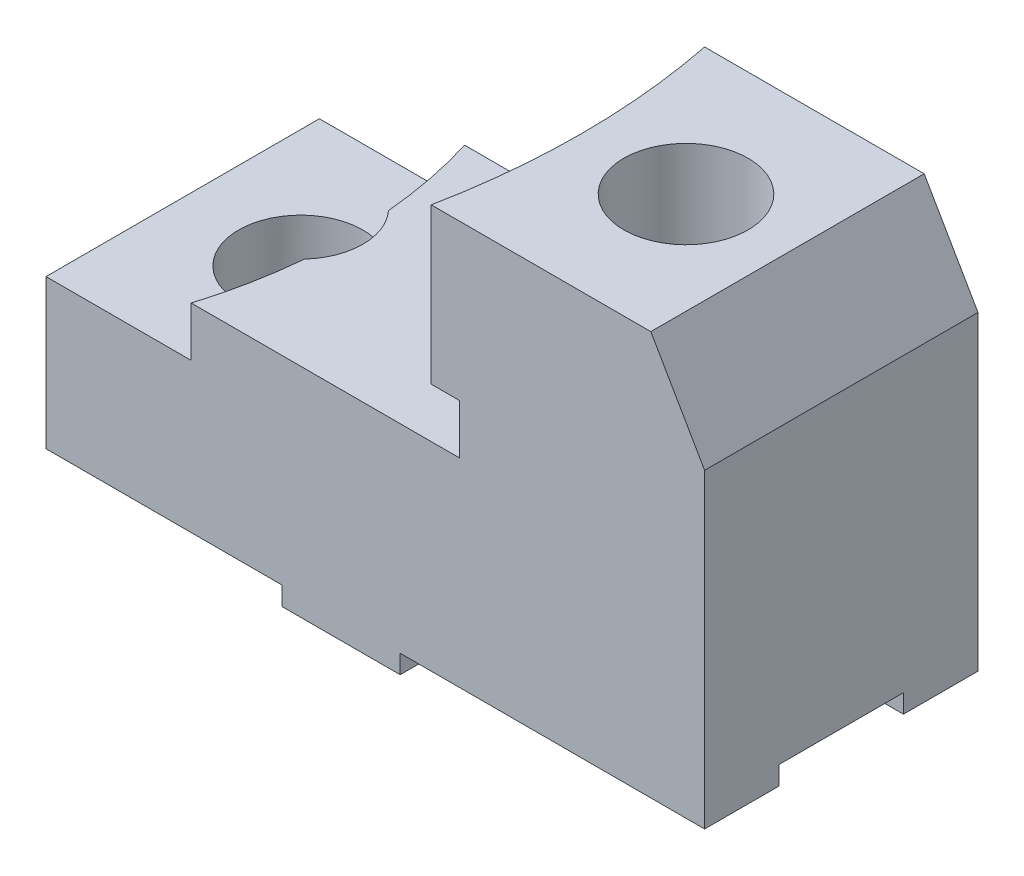
SolidWorks part; units mm, degrees
ref_plane "Front Plane" through (0, 0, 0) normal (0, 0, 1) x (1, 0, 0)
ref_plane "Top Plane" through (0, 0, 0) normal (0, 1, 0) x (1, 0, 0)
ref_plane "Right Plane" through (0, 0, 0) normal (1, 0, 0) x (0, 0, -1)
sketch "Sketch1" plane through (0, 0, 0) normal (0, 0, 1) x (1, 0, 0)
  line L0 (0, 54.6637) -> (0, -50.0258) construction
  line L1 (-88.8798, 0) -> (95.795, 0) construction
  line L10 (-47.5, -12) -> (-47.5, 12)
  line L11 (-47.5, 12) -> (58.5, 12)
  line L12 (58.5, 12) -> (58.5, -12)
  line L13 (58.5, -12) -> (9.5, -12)
  line L14 (9.5, -12) -> (9.5, -15)
  line L15 (9.5, -15) -> (-9.5, -15)
  line L16 (-9.5, -15) -> (-9.5, -12)
  line L17 (-9.5, -12) -> (-47.5, -12)
  dimension "D1" = 27
  dimension "D2" = 3
  dimension "D3" = 106
  dimension "D4" = 19
  dimension "D5" = 38
extrude "base" add sketch "Sketch1" against normal blind 44
sketch "Sketch2" plane through (0, 12, 0) normal (0, 1, 0) x (1, 0, 0)
  line L0 (-187.7294, 22) -> (123.8931, 22) construction
  line L1 (0, 66.7065) -> (0, -35.5401) construction
  line L2 (58.5, 44) -> (-47.5, 44) construction
  line L4 (-24.1272, 44) -> (14.5, 44)
  line L5 (-24.1272, 0) -> (14.5, 0)
  line L6 (58.5, 0) -> (-47.5, 0) construction
  line L7 (14.5, 44) -> (19.0851, 44)
  line L8 (14.5, 0) -> (19.0851, 0)
  line L10 (-47.5, 44) -> (-47.5, 0) construction
  arc A0 (-24.1272, 44) -> (-24.1272, 0) centre (-95.8279, 22) cw
  arc A1 (14.5, 44) -> (14.5, 0) centre (-95.8279, 22) cw
  arc A2 (14.5, 44) -> (14.5, 0) centre (-95.8279, 22) cw
  arc A3 (14.5, 44) -> (14.5, 0) centre (-95.8279, 22) cw
  arc A4 (19.0851, 0) -> (19.0851, 44) centre (-95.8279, 22) ccw
  circle A5 centre (-28.5, 22) radius 10
  circle A6 centre (-28.5, 22) radius 6.5
  line M7 (-47.5, 0) -> (58.5, 0)
  line M8 (58.5, 0) -> (58.5, 44)
  line M9 (58.5, 44) -> (-47.5, 44)
  dimension "D1" = 75
  dimension "D2" = 112.5
  dimension "D3" = 44
  dimension "D4" = 117
  dimension "D5" = 20
  dimension "D6" = 13
  dimension "D7" = 19
extrude "middle level" add sketch "Sketch2<4>" along normal blind 8 contours A5 A0 A1 M7 M9 | A4 A1 M7 M9 region at (-2.7669, 12, -22) region at (18.2114, 12, -22)
sketch "Sketch2<4>" plane through (0, 12, 0) normal (0, 1, 0) x (1, 0, 0) same geometry as "Sketch2"
extrude "up level" add sketch "Sketch2" along normal blind 41 contours A4 M7 M8 M9 region at (39.4844, 12, -22)
extrude "angle level" add sketch "Sketch2<6>" against normal blind 25 from surface contours A4 A1 M7 M9 region at (18.2114, 12, -22) starting at face at (39.3143, 53, -22)
sketch "Sketch2<6>" plane through (0, 12, 0) normal (0, 1, 0) x (1, 0, 0) same geometry as "Sketch2"
extrude "big cyl" cut sketch "Sketch2<7>" against normal blind 22 from surface contours A0 A5 | A0 A6 A5 region at (-19.9473, 12, -22) region at (-21.0948, 12, -22) starting at face at (-7.8066, 20, -22)
sketch "Sketch2<7>" plane through (0, 12, 0) normal (0, 1, 0) x (1, 0, 0) same geometry as "Sketch2"
extrude "small cyl" cut sketch "Sketch2<8>" against normal through all contours A6 region at (-28.5, 12, -22)
sketch "Sketch2<8>" plane through (0, 12, 0) normal (0, 1, 0) x (1, 0, 0) same geometry as "Sketch2"
sketch "Sketch5" plane through (0, 53, 0) normal (0, 1, 0) x (1, 0, 0)
  line L0 (-79.8364, 22) -> (59.3901, 22) construction
  line L1 (0, 60.2658) -> (0, -20.9817) construction
  line L2 (14.5, 0) -> (58.5, 0) construction
  line L3 (58.5, 44) -> (14.5, 44) construction
  circle A0 centre (33.5, 22) radius 10
  circle A1 centre (33.5, 22) radius 6.5
  dimension "D1" = 20
  dimension "D2" = 13
  dimension "D3" = 62
extrude "big cyl 2" cut sketch "Sketch5" against normal blind 22
extrude "small cyl 2" cut sketch "Sketch5<2>" against normal through all contours A1 region at (33.5, 53, -22)
sketch "Sketch5<2>" plane through (0, 53, 0) normal (0, 1, 0) x (1, 0, 0) same geometry as "Sketch5"
sketch "Sketch6" plane through (0, 0, 0) normal (0, 0, 1) x (1, 0, 0)
  line L0 (49.8397, 53) -> (58.5, 38)
  line L1 (14.5, 53) -> (58.5, 53) construction
  line L2 (58.5, -12) -> (58.5, 53) construction
  line L3 (58.5, 38) -> (58.5, 53)
  line L4 (58.5, 53) -> (49.8397, 53)
  dimension "D1" = 15
  dimension "D2" = 30
extrude "base angle" cut sketch "Sketch6" against normal through all
sketch "Sketch7" plane through (-47.5, 0, 0) normal (-1, 0, 0) x (0, 0, 1)
  line L0 (-61.0231, -12) -> (18.0242, -12) construction
  line L1 (-12, -15) -> (-12, -9)
  line L2 (-12, -9) -> (-32, -9)
  line L3 (-32, -9) -> (-32, -15)
  line L4 (-22, 56.4327) -> (-22, -27.8137) construction
  line L5 (-44, 12) -> (0, 12) construction
  line L6 (-22, 28) -> (-22, 53) construction
  line L7 (-22, -12) -> (-22, -2) construction
  line L8 (-32, -15) -> (-12, -15)
  line L9 (-44, -15) -> (0, -15) construction
  dimension "D1" = 3
  dimension "D2" = 20
  dimension "D3" = 21
extrude "down cut" cut sketch "Sketch7" against normal through all
